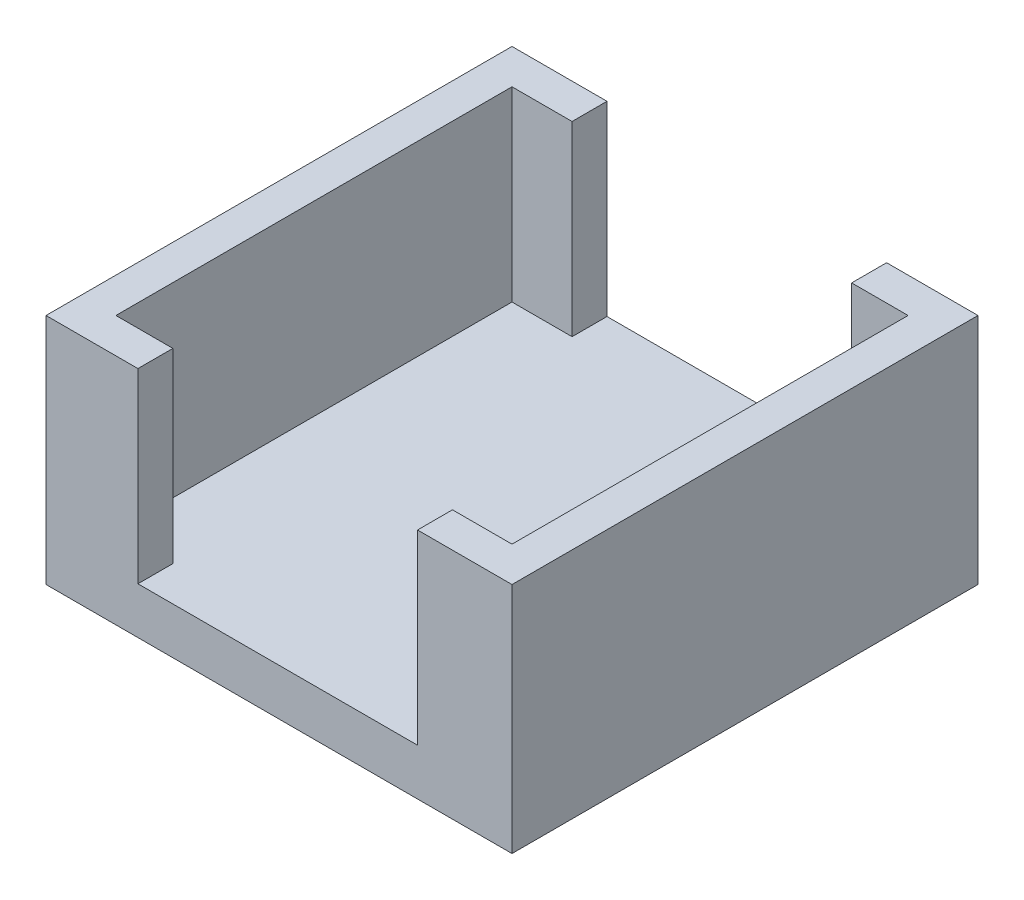
SolidWorks part; units mm, degrees
ref_plane "Front Plane" through (0, 0, 0) normal (0, 0, 1) x (1, 0, 0)
ref_plane "Top Plane" through (0, 0, 0) normal (0, 1, 0) x (1, 0, 0)
ref_plane "Right Plane" through (0, 0, 0) normal (1, 0, 0) x (0, 0, -1)
sketch "Sketch1" plane through (0, 0, 0) normal (0, 1, 0) x (1, 0, 0)
  line L0 (-1.5, 18.5) -> (18.5, 18.5)
  line L1 (0, 0) -> (17, 0)
  line L2 (0, 0) -> (0, 17)
  line L3 (0, 17) -> (17, 17)
  line L4 (17, 0) -> (17, 17)
  line L5 (18.5, -1.5) -> (18.5, 18.5)
  line L6 (-1.5, -1.5) -> (18.5, -1.5)
  line L7 (-1.5, -1.5) -> (-1.5, 18.5)
  dimension "D1" = 17
  dimension "D2" = 17
  dimension "D3" = 1.5
extrude "Boss-Extrude2" add sketch "Sketch1" along normal blind 2 contours L1 L4 L3 L2 | L7 L6 L5 L0 L4 L1 L2 L3 region at (8.5, 0, -18.2172) region at (8.5, 0, -8.5)
extrude "Boss-Extrude3" add sketch "Sketch1<4>" along normal blind 10
sketch "Sketch1<4>" plane through (0, 0, 0) normal (0, 1, 0) x (1, 0, 0) same geometry as "Sketch1"
sketch "Sketch2" plane through (0, 10, 0) normal (0, 1, 0) x (1, 0, 0)
  line L0 (18.5, 18.5) -> (-1.5, 18.5) construction
  line L1 (2.5776, 18.5) -> (14.5776, 18.5)
  line L2 (2.5776, 18.5) -> (2.5776, 17)
  line L3 (2.5776, 17) -> (14.5776, 17)
  line L4 (14.5776, 18.5) -> (14.5776, 17)
  line L5 (17, 17) -> (0, 17) construction
  line L6 (0, 0) -> (17, 0) construction
  line L7 (2.4454, 0) -> (14.4454, 0)
  line L8 (2.4454, 0) -> (2.4454, -1.5)
  line L9 (2.4454, -1.5) -> (14.4454, -1.5)
  line L10 (14.4454, 0) -> (14.4454, -1.5)
  line L11 (-1.5, -1.5) -> (18.5, -1.5) construction
  dimension "D1" = 12
  dimension "D2" = 12
extrude "Cut-Extrude1" cut sketch "Sketch2" against normal up to surface (8 mm away) up to face at (8.5, 2, -8.5)
